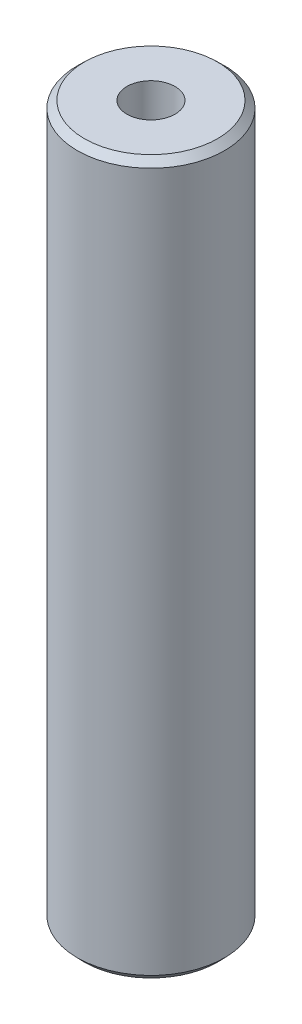
SolidWorks part; units mm, degrees
ref_plane "Front Plane" through (0, 0, 0) normal (0, 0, 1) x (1, 0, 0)
ref_plane "Top Plane" through (0, 0, 0) normal (0, 1, 0) x (1, 0, 0)
ref_plane "Right Plane" through (0, 0, 0) normal (1, 0, 0) x (0, 0, -1)
sketch "Sketch1" plane through (0, 0, 0) normal (0, 1, 0) x (1, 0, 0)
  circle A0 centre (0, 0) radius 25
  dimension "SHAFT_OD" = 50
extrude "Boss-Extrude1" add sketch "Sketch1" along normal blind 242.0612
sketch "Sketch2" plane through (0, 0, 0) normal (0, 1, 0) x (1, 0, 0)
  circle A0 centre (0, 0) radius 8.1753
  dimension "BORE_D" = 16.3506
extrude "Cut-Extrude1" cut sketch "Sketch2" along normal through all
chamfer "Chamfer1" distance 2.309 angle 46.152 2 edges at (0, 242.0612, 25) (0, 0, 25) first distance on face at (0, 242.0612, 25) first distance on face at (0, 0, 8.1753)
